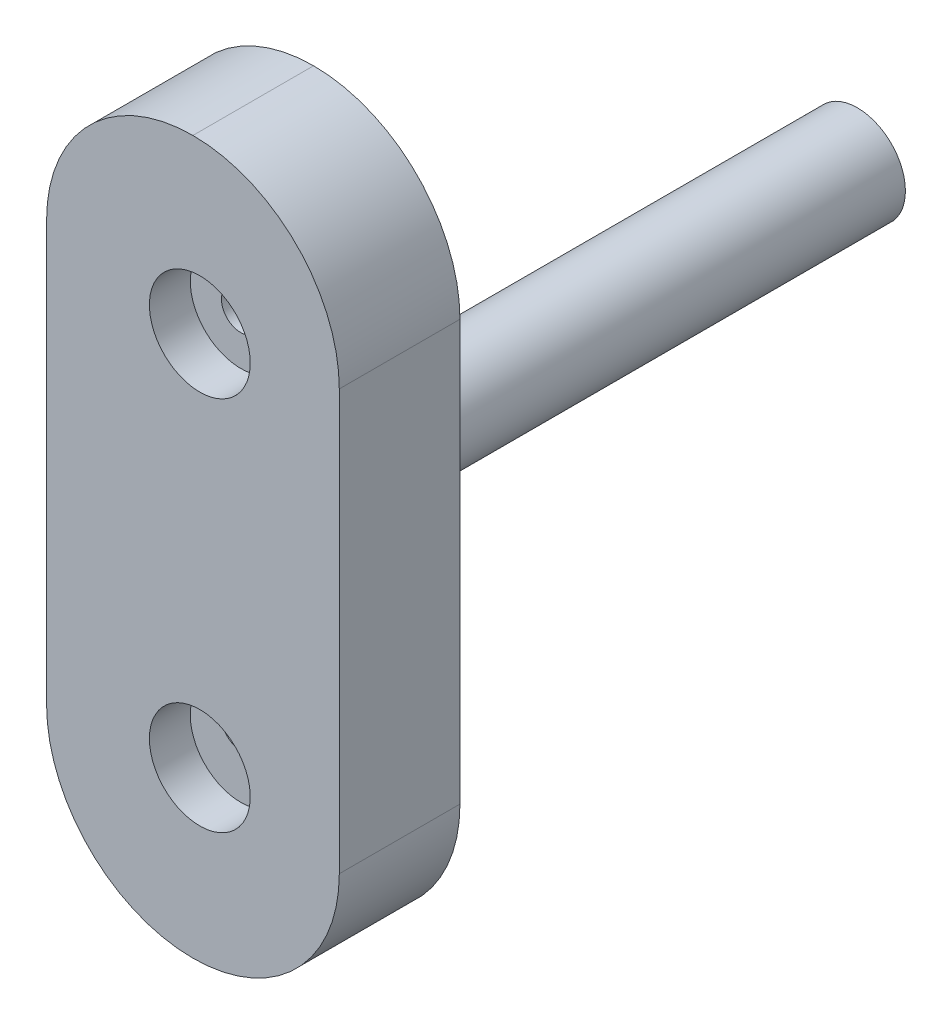
SolidWorks part; units mm, degrees
material "PLA"
ref_plane "Front Plane" through (0, 0, 0) normal (0, 0, 1) x (1, 0, 0)
ref_plane "Top Plane" through (0, 0, 0) normal (0, 1, 0) x (1, 0, 0)
ref_plane "Right Plane" through (0, 0, 0) normal (1, 0, 0) x (0, 0, -1)
sketch "Sketch1" plane through (0, 0, 0) normal (0, 0, 1) x (1, 0, 0)
  circle A0 centre (0, 0) radius 3.98
  dimension "D1" = 7.96
extrude "Boss-Extrude1" add sketch "Sketch1" along normal blind 54.5
sketch "Sketch3" plane through (0, 0, 54.5) normal (0, 0, 1) x (1, 0, 0)
  line L1 (-12.7, -30.1) -> (11.56, -30.1)
  line L2 (-12.7, -30.1) -> (-12.7, 28.96)
  line L3 (-12.7, 28.96) -> (11.56, 28.96)
  line L4 (11.56, -30.1) -> (11.56, 28.96)
  line L5 (-12.7, -30.1) -> (11.56, 28.96) construction
  line L6 (-12.7, 28.96) -> (11.56, -30.1) construction
  dimension "D1" = 28.96
  dimension "D2" = 24.26
  dimension "D3" = 59.06
  dimension "D4" = 11.56
extrude "Boss-Extrude2" add sketch "Sketch3" against normal blind 10
sketch "Sketch4" plane through (0, 0, 44.5) normal (0, 0, -1) x (-1, 0, 0)
  line L0 (-11.4909, 0) -> (12.9329, 0) construction
  line L1 (0, 20.8854) -> (0, -12.302) construction
  circle A0 centre (0, 15) radius 1.6
  circle A1 centre (0, -15) radius 1.6
  dimension "D1" = 15
  dimension "D2" = 3.2
extrude "Cut-Extrude1" cut sketch "Sketch4" against normal through all
sketch "Croquis2" plane through (0, 0, 54.5) normal (0, 0, 1) x (1, 0, 0)
  line L0 (-12.7, -0.57) -> (11.56, -0.57) construction
  line L1 (-12.7, 28.96) -> (-12.7, -30.1) construction
  line L2 (11.56, -30.1) -> (11.56, 28.96) construction
  circle A0 centre (0, 15) radius 4.18
  circle A1 centre (0, -16.14) radius 4.18
  dimension "D1" = 8.36
extrude "Cortar-Extruir2" cut sketch "Croquis2" against normal blind 3.39
fillet "Redondeo1" radius 12.13 4 edges at (11.56, -30.1, 49.5) (-12.7, -30.1, 49.5) (-12.7, 28.96, 49.5) (11.56, 28.96, 49.5)
